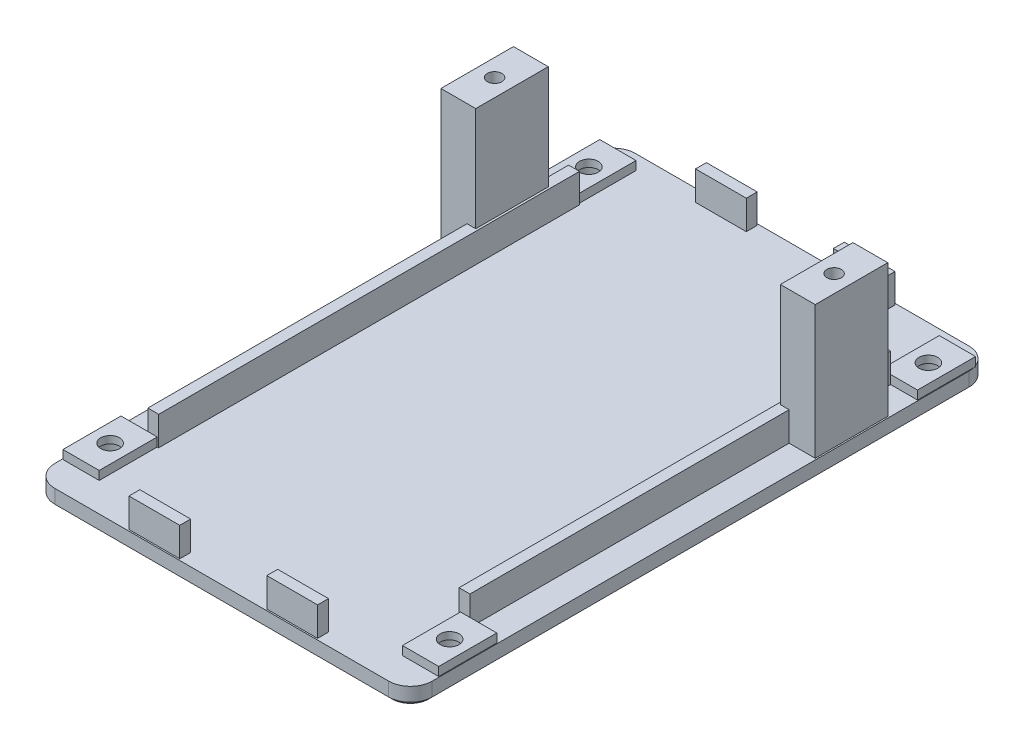
SolidWorks part; units mm, degrees
ref_plane "Front Plane" through (0, 0, 0) normal (0, 0, 1) x (1, 0, 0)
ref_plane "Top Plane" through (0, 0, 0) normal (0, 1, 0) x (1, 0, 0)
ref_plane "Right Plane" through (0, 0, 0) normal (1, 0, 0) x (0, 0, -1)
sketch "Sketch1" plane through (0, 0, 0) normal (0, 1, 0) x (1, 0, 0)
  line L0 (-23, 54) -> (23, 54)
  line L1 (26, 51) -> (26, -23)
  line L2 (23, -26) -> (-23, -26)
  line L3 (-26, -23) -> (-26, 51)
  arc A0 (-26, 51) -> (-23, 54) centre (-23, 51) cw
  arc A1 (23, 54) -> (26, 51) centre (23, 51) cw
  arc A2 (26, -23) -> (23, -26) centre (23, -23) cw
  arc A3 (-23, -26) -> (-26, -23) centre (-23, -23) cw
extrude "Boss-Extrude1" add sketch "Sketch1" along normal blind 2.4
chamfer "Chamfer1" distance 0.5 angle 45 8 edges at (0, 0, -54) (-25.1213, 0, -53.1213) (25.1213, 0, -53.1213) (-26, 0, -14) (26, 0, -14) (-25.1213, 0, 25.1213) (25.1213, 0, 25.1213) (0, 0, 26)
sketch "Sketch2" plane through (0, 0, 0) normal (0, 0, 1) x (1, 0, 0)
  line L1 (-25.9, 2.39) -> (-20.9, 2.39)
  line L2 (-25.9, 2.39) -> (-25.9, 3.6)
  line L3 (-25.9, 3.6) -> (-20.9, 3.6)
  line L4 (-20.9, 2.39) -> (-20.9, 3.6)
extrude "Boss-Extrude2" add sketch "Sketch2" along normal blind 8 from offset 52 offset against normal yes
sketch "Sketch3" plane through (0, 0, 0) normal (0, 0, 1) x (1, 0, 0)
  line L1 (-25.9, 2.39) -> (-20.9, 2.39)
  line L2 (-25.9, 2.39) -> (-25.9, 3.6)
  line L3 (-25.9, 3.6) -> (-20.9, 3.6)
  line L4 (-20.9, 2.39) -> (-20.9, 3.6)
extrude "Boss-Extrude3" add sketch "Sketch3" along normal blind 8 from offset 14
sketch "Sketch4" plane through (0, 0, 0) normal (0, 0, 1) x (1, 0, 0)
  line L1 (20.9, 2.39) -> (25.9, 2.39)
  line L2 (20.9, 2.39) -> (20.9, 3.6)
  line L3 (20.9, 3.6) -> (25.9, 3.6)
  line L4 (25.9, 2.39) -> (25.9, 3.6)
extrude "Boss-Extrude4" add sketch "Sketch4" along normal blind 8 from offset 52 offset against normal yes
sketch "Sketch5" plane through (0, 0, 0) normal (0, 0, 1) x (1, 0, 0)
  line L1 (20.9, 2.39) -> (25.9, 2.39)
  line L2 (20.9, 2.39) -> (20.9, 3.6)
  line L3 (20.9, 3.6) -> (25.9, 3.6)
  line L4 (25.9, 2.39) -> (25.9, 3.6)
extrude "Boss-Extrude5" add sketch "Sketch5" along normal blind 8 from offset 14
sketch "Sketch6" plane through (0, 0, 0) normal (0, 0, 1) x (1, 0, 0)
  line L1 (-22.2, 2.39) -> (-20.7, 2.39)
  line L2 (-22.2, 2.39) -> (-22.2, 6.4)
  line L3 (-22.2, 6.4) -> (-20.7, 6.4)
  line L4 (-20.7, 2.39) -> (-20.7, 6.4)
extrude "Boss-Extrude6" add sketch "Sketch6" along normal blind 58 from offset 44 offset against normal yes
sketch "Sketch7" plane through (0, 0, 0) normal (0, 0, 1) x (1, 0, 0)
  line L1 (-25.8, 2.39) -> (-21, 2.39)
  line L2 (-25.8, 2.39) -> (-25.8, 20.75)
  line L3 (-25.8, 20.75) -> (-21, 20.75)
  line L4 (-21, 2.39) -> (-21, 20.75)
extrude "Boss-Extrude7" add sketch "Sketch7" along normal blind 10 from offset 40 offset against normal yes
sketch "Sketch8" plane through (0, 0, 0) normal (0, 1, 0) x (1, 0, 0)
  circle A0 centre (-23.4, 35) radius 1
extrude "Boss-Extrude8" add sketch "Sketch8" along normal blind 13.75 from offset 8 separate body
combine bodies "Combine1" operation type subtract main body 107 bodies to subtract 108
sketch "Sketch9" plane through (0, 0, 0) normal (0, 0, 1) x (1, 0, 0)
  line L1 (-13, 2.39) -> (-6, 2.39)
  line L2 (-13, 2.39) -> (-13, 6.4)
  line L3 (-13, 6.4) -> (-6, 6.4)
  line L4 (-6, 2.39) -> (-6, 6.4)
extrude "Boss-Extrude9" add sketch "Sketch9" along normal blind 1.5 from offset 53.8 offset against normal yes
sketch "Sketch10" plane through (0, 0, 0) normal (0, 0, 1) x (1, 0, 0)
  line L1 (-13, 2.39) -> (-6, 2.39)
  line L2 (-13, 2.39) -> (-13, 6.4)
  line L3 (-13, 6.4) -> (-6, 6.4)
  line L4 (-6, 2.39) -> (-6, 6.4)
extrude "Boss-Extrude10" add sketch "Sketch10" along normal blind 1.5 from offset 24.3
sketch "Sketch11" plane through (0, 0, 0) normal (0, 0, 1) x (1, 0, 0)
  line L1 (20.7, 2.39) -> (22.2, 2.39)
  line L2 (20.7, 2.39) -> (20.7, 6.4)
  line L3 (20.7, 6.4) -> (22.2, 6.4)
  line L4 (22.2, 2.39) -> (22.2, 6.4)
extrude "Boss-Extrude11" add sketch "Sketch11" along normal blind 58 from offset 44 offset against normal yes
sketch "Sketch12" plane through (0, 0, 0) normal (0, 0, 1) x (1, 0, 0)
  line L1 (21, 2.39) -> (25.8, 2.39)
  line L2 (21, 2.39) -> (21, 20.75)
  line L3 (21, 20.75) -> (25.8, 20.75)
  line L4 (25.8, 2.39) -> (25.8, 20.75)
extrude "Boss-Extrude12" add sketch "Sketch12" along normal blind 10 from offset 40 offset against normal yes
sketch "Sketch13" plane through (0, 0, 0) normal (0, 1, 0) x (1, 0, 0)
  circle A0 centre (23.4, 35) radius 1
extrude "Boss-Extrude13" add sketch "Sketch13" along normal blind 13.75 from offset 8 separate body
combine bodies "Combine2" operation type subtract main body 113 bodies to subtract 114
sketch "Sketch14" plane through (0, 0, 0) normal (0, 0, 1) x (1, 0, 0)
  line L1 (6, 2.39) -> (13, 2.39)
  line L2 (6, 2.39) -> (6, 6.4)
  line L3 (6, 6.4) -> (13, 6.4)
  line L4 (13, 2.39) -> (13, 6.4)
extrude "Boss-Extrude14" add sketch "Sketch14" along normal blind 1.5 from offset 53.8 offset against normal yes
sketch "Sketch15" plane through (0, 0, 0) normal (0, 0, 1) x (1, 0, 0)
  line L1 (6, 2.39) -> (13, 2.39)
  line L2 (6, 2.39) -> (6, 6.4)
  line L3 (6, 6.4) -> (13, 6.4)
  line L4 (13, 2.39) -> (13, 6.4)
extrude "Boss-Extrude15" add sketch "Sketch15" along normal blind 1.5 from offset 24.3
sketch "Sketch16" plane through (0, 0, 0) normal (0, 1, 0) x (1, 0, 0)
  circle A0 centre (-23.4, 48) radius 2.1
extrude "Boss-Extrude16" add sketch "Sketch16" along normal blind 3.6 from offset 1 separate body offset against normal yes
combine bodies "Combine3" operation type subtract main body 117 bodies to subtract 118
sketch "Sketch17" plane through (0, 0, 0) normal (0, 1, 0) x (1, 0, 0)
  circle A0 centre (-23.4, 48) radius 1.3
extrude "Boss-Extrude17" add sketch "Sketch17" along normal blind 1.2 from offset 2.5 separate body
combine bodies "Combine4" operation type subtract main body 119 bodies to subtract 120
sketch "Sketch18" plane through (0, 0, 0) normal (0, 1, 0) x (1, 0, 0)
  circle A0 centre (-23.4, -18) radius 2.1
extrude "Boss-Extrude18" add sketch "Sketch18" along normal blind 3.6 from offset 1 separate body offset against normal yes
combine bodies "Combine5" operation type subtract main body 121 bodies to subtract 122
sketch "Sketch19" plane through (0, 0, 0) normal (0, 1, 0) x (1, 0, 0)
  circle A0 centre (-23.4, -18) radius 1.3
extrude "Boss-Extrude19" add sketch "Sketch19" along normal blind 1.2 from offset 2.5 separate body
combine bodies "Combine6" operation type subtract main body 123 bodies to subtract 124
sketch "Sketch20" plane through (0, 0, 0) normal (0, 1, 0) x (1, 0, 0)
  circle A0 centre (23.4, 48) radius 2.1
extrude "Boss-Extrude20" add sketch "Sketch20" along normal blind 3.6 from offset 1 separate body offset against normal yes
combine bodies "Combine7" operation type subtract main body 125 bodies to subtract 126
sketch "Sketch21" plane through (0, 0, 0) normal (0, 1, 0) x (1, 0, 0)
  circle A0 centre (23.4, 48) radius 1.3
extrude "Boss-Extrude21" add sketch "Sketch21" along normal blind 1.2 from offset 2.5 separate body
combine bodies "Combine8" operation type subtract main body 127 bodies to subtract 128
sketch "Sketch22" plane through (0, 0, 0) normal (0, 1, 0) x (1, 0, 0)
  circle A0 centre (23.4, -18) radius 2.1
extrude "Boss-Extrude22" add sketch "Sketch22" along normal blind 3.6 from offset 1 separate body offset against normal yes
combine bodies "Combine9" operation type subtract main body 129 bodies to subtract 130
sketch "Sketch23" plane through (0, 0, 0) normal (0, 1, 0) x (1, 0, 0)
  circle A0 centre (23.4, -18) radius 1.3
extrude "Boss-Extrude23" add sketch "Sketch23" along normal blind 1.2 from offset 2.5 separate body
combine bodies "Combine10" operation type subtract main body 131 bodies to subtract 132
sketch "Sketch24" plane through (0, 0, 0) normal (0, 0, 1) x (1, 0, 0)
  line L1 (-2, -0.1) -> (2, -0.1)
  line L2 (-2, -0.1) -> (-2, 0.8)
  line L3 (-2, 0.8) -> (2, 0.8)
  line L4 (2, -0.1) -> (2, 0.8)
extrude "Boss-Extrude24" add sketch "Sketch24" along normal blind 1 from offset 54.1 separate body offset against normal yes
combine bodies "Combine11" operation type subtract main body 133 bodies to subtract 134
